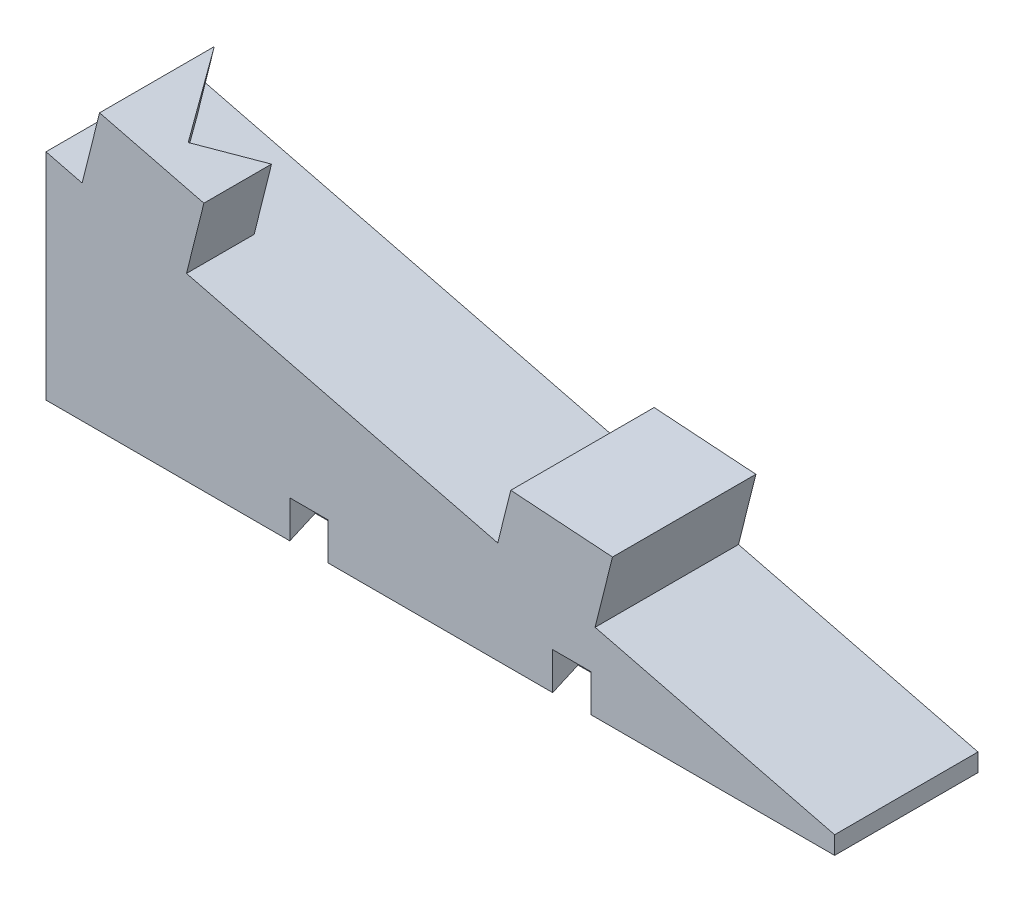
SolidWorks part; units mm, degrees
ref_plane "Front Plane" through (0, 0, 0) normal (0, 0, 1) x (1, 0, 0)
ref_plane "Top Plane" through (0, 0, 0) normal (0, 1, 0) x (1, 0, 0)
ref_plane "Right Plane" through (0, 0, 0) normal (1, 0, 0) x (0, 0, -1)
sketch "Sketch1" plane through (0, 0, 0) normal (0, 0, 1) x (1, 0, 0)
  line L0 (-55, 21.875) -> (55, -5.625)
  line L1 (0, 8.125) -> (0, -8.125) construction
  line L2 (-55, 21.875) -> (-55, -8.125)
  line L3 (-55, -8.125) -> (55, -8.125)
  line L4 (55, -5.625) -> (55, -8.125)
  point P3 (65, -8.125)
  point P7 (0, 0)
  dimension "D1" = 110
  dimension "D2" = 10
  dimension "D3" = 30
extrude "Boss-Extrude1" add sketch "Sketch1" along normal blind 10 and the other way blind 10
sketch "Sketch2" plane through (1.9118, 7.6471, 0) normal (0.2425, 0.9701, 0) x (0.9701, -0.2425, 0)
  line L0 (-80.1847, 0) -> (-56.0217, 0) construction
  line L1 (-58.6633, 10) -> (-58.6633, -10) construction
  line L2 (-53.4633, 6) -> (-53.4633, -10) construction
  line L3 (-53.4633, -10) -> (-38.4633, -10)
  line L5 (-53.4633, 6) -> (-45.408, -5.4504)
  line L6 (54.7221, -10) -> (-58.6633, -10) construction
  line L7 (54.7221, 10) -> (-58.6633, 10) construction
  line L10 (-53.4633, -10) -> (-53.4633, 6)
  line L11 (-45.408, -5.4504) -> (-38.4633, -0.5649)
  line L12 (6.2867, 10) -> (6.2867, -10)
  line L13 (-38.4633, -0.5649) -> (-38.4633, -10)
  line L17 (20.2867, 10) -> (6.2867, 10)
  line L18 (20.2867, 10) -> (20.2867, -10)
  line L19 (20.2867, -10) -> (6.2867, -10)
  dimension "D1" = 5.2
  dimension "D2" = 14
  dimension "D3" = 15
  dimension "D4" = 73.75
  dimension "D5" = 14
  dimension "D6" = 16
  dimension "D10" = 35.126
extrude "Boss-Extrude2" add sketch "Sketch2" along normal blind 10
sketch "Sketch3" plane through (0, -8.125, 0) normal (0, -1, 0) x (1, 0, 0)
  line L0 (55, -10) -> (55, 10) construction
  line L1 (-55, 10) -> (55, 10) construction
  line L2 (-55, -10) -> (-55, 10) construction
  line L6 (0, 0) -> (-55, 0) construction
  line L7 (18.3333, 4.9) -> (55, 4.9) construction
  line L8 (-18.3333, 4.9) -> (18.3333, 4.9) construction
  line L9 (-18.3333, 4.9) -> (-55, 4.9) construction
  point P7 (18.3333, 4.9)
  point P9 (-18.3333, 4.9)
  line B0 (15.6921, 10.0585) -> (14.1129, 4.9)
  line B1 (14.1129, 4.9) -> (22.5537, 4.9)
  line B2 (22.5537, 4.9) -> (20.9746, 10.0585)
  line B3 (20.9746, 10.0585) -> (15.6921, 10.0585)
  line B4 (-20.7833, 10) -> (-15.8833, 10) construction
  line B5 (-20.9746, 10.0585) -> (-22.5537, 4.9)
  line B6 (-22.5537, 4.9) -> (-14.1129, 4.9)
  line B7 (-14.1129, 4.9) -> (-15.6921, 10.0585)
  line B8 (-15.6921, 10.0585) -> (-20.9746, 10.0585)
sketch_block_instance "Block1-3"
sketch_block "Block1"
sketch_block_instance "Block1-4"
extrude "Cut-Extrude1" cut sketch "Sketch3" against normal blind 5.2
sketch "Sketch4" plane through (0, 0, 10) normal (0, 0, 1) x (1, 0, 0)
  line L0 (9.8298, 13.3984) -> (10.4361, 15.8237)
  line L1 (10.4361, 15.8237) -> (8.0108, 6.1223) construction
  line L2 (10.4361, 15.8237) -> (24.0181, 12.4282)
  line L3 (24.0181, 12.4282) -> (9.8298, 13.3984)
  dimension "D1" = 2.5
extrude "Cut-Extrude2" cut sketch "Sketch4" against normal blind 20
